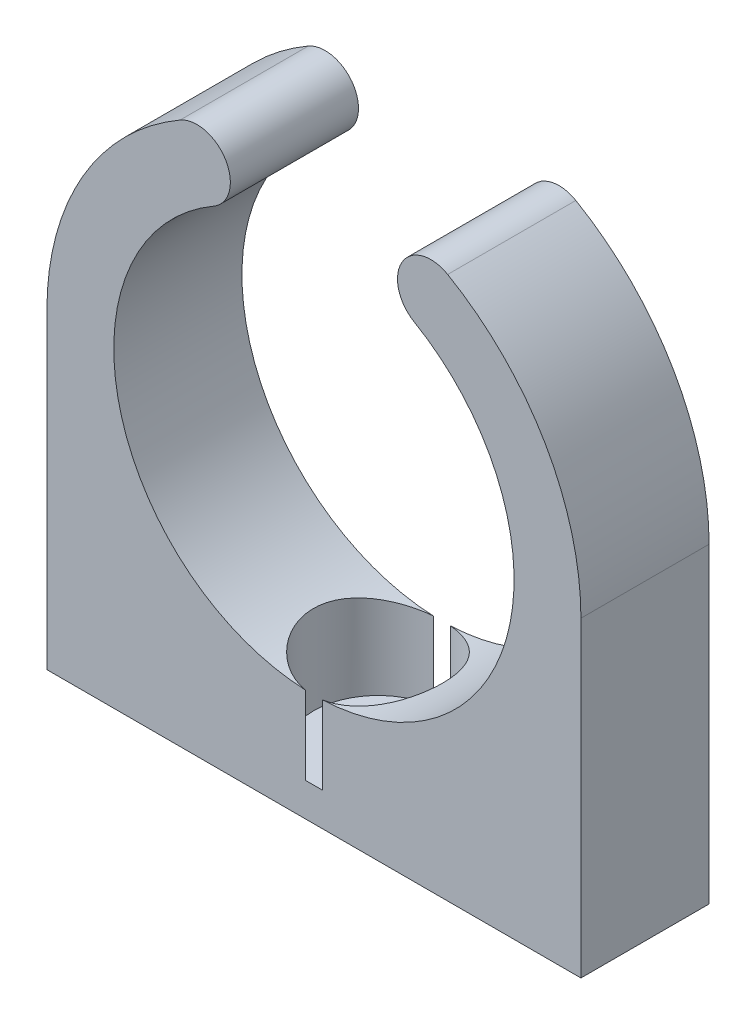
SolidWorks part; units mm, degrees
material "Thornel Mat VMA"
ref_plane "Front Plane" through (0, 0, 0) normal (0, 0, 1) x (1, 0, 0)
ref_plane "Top Plane" through (0, 0, 0) normal (0, 1, 0) x (1, 0, 0)
ref_plane "Right Plane" through (0, 0, 0) normal (1, 0, 0) x (0, 0, -1)
sketch "Sketch1" plane through (0, 0, 0) normal (0, 0, 1) x (1, 0, 0)
  line L0 (-11.98, -13.98) -> (11.98, -13.98)
  line L1 (11.98, -13.98) -> (11.98, 0)
  line L2 (-11.98, -13.98) -> (-11.98, 0)
  circle A0 centre (0, 0) radius 9 construction
  arc A1 (-8.98, 0) -> (4.4986, 7.772) centre (0, 0) ccw
  arc A2 (11.98, 0) -> (6.0014, 10.3684) centre (0, 0) ccw
  arc A3 (-4.4986, 7.772) -> (-6.0014, 10.3684) centre (-5.25, 9.0702) ccw
  circle A4 centre (0, 0) radius 11.98 construction
  circle A5 centre (0, 0) radius 8.98 construction
  arc A6 (6.0014, 10.3684) -> (4.4986, 7.772) centre (5.25, 9.0702) ccw
  arc A7 (-4.4986, 7.772) -> (-8.98, 0) centre (0, 0) ccw
  arc A8 (-6.0014, 10.3684) -> (-11.98, 0) centre (0, 0) ccw
  point P10 (0, -13.98)
  point P17 (13.4074, 4.0991)
  point P22 (8.6259, 2.6372)
  dimension "D1" = 18
  dimension "D7" = 7.5
  dimension "D4" = 5
  dimension "D3" = 3
extrude "Boss-Extrude1" add sketch "Sketch1" along normal mid plane 5.75 contours L1 A2 L2 L0 A1 region at (-11.637, -6.99, 0)
sketch "Sketch4" plane through (0, 0, 0) normal (0, 0, 1) x (1, 0, 0)
  line L0 (1.5, -12.48) -> (2.9, -12.48)
  line L1 (-2.9, -7.48) -> (2.9, -7.48)
  line L2 (-2.9, -7.48) -> (-2.9, -12.48)
  line L3 (-2.9, -12.48) -> (-1.5, -12.48)
  line L4 (2.9, -7.48) -> (2.9, -12.48)
  line L5 (-2.9, -7.48) -> (2.9, -12.48) construction
  line L6 (-2.9, -12.48) -> (2.9, -7.48) construction
  line L8 (-1.5, -12.48) -> (-1.5, -13.98)
  line L9 (-1.5, -13.98) -> (1.5, -13.98)
  line L10 (1.5, -12.48) -> (1.5, -13.98)
  line L11 (-1.5, -12.48) -> (1.5, -13.98) construction
  line L12 (-1.5, -13.98) -> (1.5, -12.48) construction
  line L13 (-11.98, -13.98) -> (11.98, -13.98) construction
  line L14 (0, -13.98) -> (0, -7.48)
  arc A2 (-4.4986, 7.772) -> (4.4986, 7.772) centre (0, 0) ccw construction
  point P0 (0, -9.98)
  point P5 (0, -13.23)
  dimension "D3" = 3
  dimension "D1" = 5.8
  dimension "D4" = 3.5
  dimension "D2" = 5
revolve "Cut-Revolve1" cut sketch "Sketch4" angle 360 about L14
equation "\"diam\"= 18mm"
equation "\"width\"= 5.75"
equation "\"D1@Sketch1\"=\"diam\""
equation "\"tolerance\"= 0.02"
equation "\"D2@Sketch1\"=\"tolerance\""
equation "\"D1@Boss-Extrude1\"=\"width\""
equation "\"bolt_outer diam\"= 5.8mm"
equation "\"bolt diam\"= 3"
equation "\"bolt head thickness\"= 3.5"
equation "\"D1@Sketch4\"=\"bolt_outer diam\""
equation "\"D3@Sketch4\"=\"bolt diam\""
equation "\"D4@Sketch4\"=\"bolt head thickness\""
